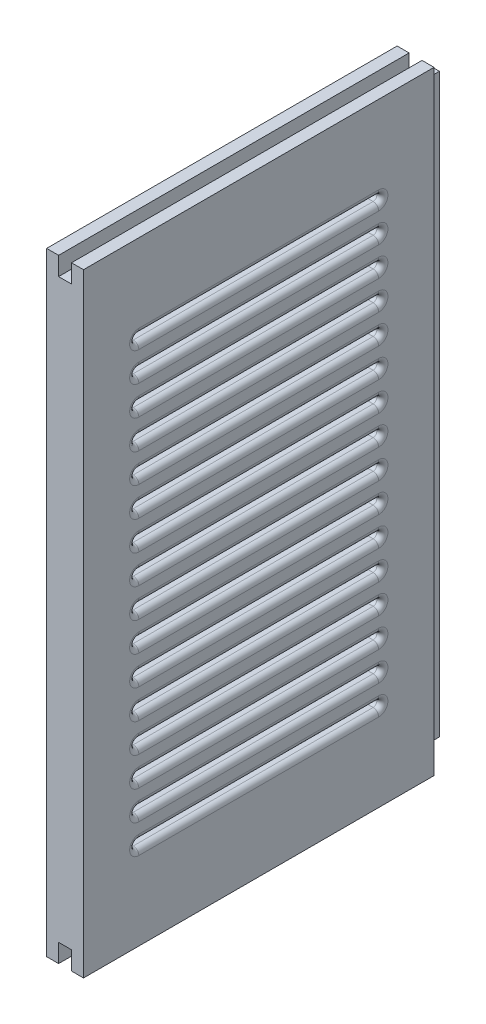
SolidWorks part; units mm, degrees
ref_plane "Front Plane" through (0, 0, 0) normal (1, 0, 0) x (0, 1, 0)
ref_plane "Top Plane" through (0, 0, 0) normal (0, 0, 1) x (0, 1, 0)
ref_plane "Right Plane" through (0, 0, 0) normal (0, 1, 0) x (-1, 0, 0)
sketch "Sketch1" plane through (0, 0, 0) normal (1, 0, 0) x (0, 1, 0)
  line L1 (0, 0) -> (166.25, 0)
  line L2 (0, 0) -> (0, 95)
  line L3 (0, 95) -> (166.25, 95)
  line L4 (166.25, 0) -> (166.25, 95)
  dimension "D1" = 166.25
  dimension "D2" = 95
extrude "Boss-Extrude1" add sketch "Sketch1" against normal blind 10
sketch "Sketch2" plane through (0, 166.25, 0) normal (0, 1, 0) x (-1, 0, 0)
  line L0 (0, 0) -> (3.35, 0) construction
  line L1 (0, 0) -> (0, -4.8) construction
  line L2 (0, -4.8) -> (3.35, -4.8) construction
  line L3 (3.35, 0) -> (3.35, -4.8) construction
  line L4 (10, 0) -> (6.65, 0) construction
  line L5 (10, 0) -> (10, -4.8) construction
  line L6 (10, -4.8) -> (6.65, -4.8) construction
  line L7 (6.65, 0) -> (6.65, -4.8) construction
  line L8 (6.65, -4.8) -> (3.35, -4.8)
  line L9 (6.65, -4.8) -> (6.65, 0)
  line L10 (6.65, 0) -> (3.35, 0)
  line L11 (3.35, -4.8) -> (3.35, 0)
  line L14 (10, 0) -> (0, 0) construction
  dimension "D1" = 3.35
  dimension "D2" = 3.35
  dimension "D3" = 4.8
extrude "Boss-Extrude2" add sketch "Sketch2" against normal up to surface (166.25 mm away) up to face at (-5, 0, 47.5)
ref_plane "Plane1" through (0, 83.125, 0) normal (0, 1, 0) x (1, 0, 0)
sketch "Sketch3" plane through (0, 166.25, 0) normal (0, 1, 0) x (-1, 0, 0)
  line L0 (0, 95) -> (3.25, 95) construction
  line L1 (0, 95) -> (0, -4.8) construction
  line L2 (0, -4.8) -> (3.25, -4.8) construction
  line L3 (3.25, 95) -> (3.25, -4.8) construction
  line L4 (6.75, -4.8) -> (10, -4.8) construction
  line L5 (6.75, -4.8) -> (6.75, 95) construction
  line L6 (6.75, 95) -> (10, 95) construction
  line L7 (10, -4.8) -> (10, 95) construction
  line L8 (3.25, 95) -> (6.75, 95)
  line L9 (3.25, 95) -> (3.25, -4.8)
  line L10 (3.25, -4.8) -> (6.75, -4.8)
  line L11 (6.75, 95) -> (6.75, -4.8)
  line L14 (10, 95) -> (0, 95) construction
  line L16 (3.35, -4.8) -> (6.65, -4.8) construction
  dimension "D1" = 3.25
  dimension "D2" = 3.25
extrude "Cut-Extrude1" cut sketch "Sketch3" against normal blind 5
mirror "Mirror1" about plane through (0, 83.125, 0) normal (0, 1, 0) of "Cut-Extrude1"
sketch "Sketch4" plane through (-10, 0, 0) normal (-1, 0, 0) x (0, -1, 0)
  line L0 (-166.25, 95) -> (0, 95) construction
  line L1 (-161.25, 0) -> (-5, 0)
  line L2 (-161.25, 0) -> (-161.25, 95)
  line L3 (-161.25, 95) -> (-5, 95)
  line L4 (-5, 0) -> (-5, 95)
  line L5 (-156.25, 5) -> (-156.25, 90)
  line L6 (-156.25, 90) -> (-10, 90)
  line L7 (-10, 5) -> (-10, 90)
  line L8 (-156.25, 5) -> (-10, 5)
  dimension "D1" = 5
extrude "Cut-Extrude2" cut sketch "Sketch4" against normal blind 5 contours L5 L8 L7 L6 region at (-10, 83.125, 47.5)
chamfer "Chamfer1" distance 5 distance2 2.5 4 edges at (-10, 10, 47.5) (-10, 83.125, 5) (-10, 156.25, 47.5) (-10, 83.125, 90) first distance on face at (-7.5, 10, 47.5) first distance on face at (-7.5, 83.125, 5) first distance on face at (-7.5, 156.25, 47.5) first distance on face at (-7.5, 83.125, 90)
sketch "Sketch5" plane through (-5, 0, 0) normal (-1, 0, 0) x (0, -1, 0)
  line L0 (-10, 5) -> (-10, 90) construction
  line L1 (-156.25, 90) -> (-10, 90) construction
  line L2 (-156.25, 90) -> (-156.25, 80) construction
  line L3 (-156.25, 80) -> (-10, 80) construction
  line L4 (-10, 90) -> (-10, 80) construction
  line L5 (-156.25, 5) -> (-156.25, 90) construction
  line L6 (-10, 80) -> (-156.25, 80) construction
  line L7 (-10, 80) -> (-10, 15) construction
  line L8 (-10, 15) -> (-156.25, 15) construction
  line L9 (-156.25, 80) -> (-156.25, 15) construction
  line L10 (-142.5, 80) -> (-142.5, 15) construction
  line L11 (-156.25, 15) -> (-10, 15) construction
  line L12 (-156.25, 15) -> (-156.25, 5) construction
  line L13 (-156.25, 5) -> (-10, 5) construction
  line L14 (-10, 15) -> (-10, 5) construction
  line L15 (-141.5, 80) -> (-141.5, 15)
  line L16 (-143.5, 80) -> (-143.5, 15)
  line L18 (-166.25, 95) -> (-142.5, 95) construction
  line L19 (-166.25, 95) -> (-166.25, 80) construction
  line L20 (-166.25, 80) -> (-142.5, 80) construction
  line L21 (-142.5, 95) -> (-142.5, 80) construction
  arc A0 (-141.5, 80) -> (-143.5, 80) centre (-142.5, 80) ccw
  arc A1 (-143.5, 15) -> (-141.5, 15) centre (-142.5, 15) ccw
  point P16 (-142.5, 47.5)
  dimension "D1" = 10
  dimension "D3" = 146.25
  dimension "D4" = 23.75
extrude "Cut-Extrude3" cut sketch "Sketch5" against normal up to next
fillet "Fillet1" radius 1.5 8 edges at (0, 142.5, 81) (0, 143.5, 47.5) (0, 142.5, 14) (-5, 142.5, 81) (-5, 141.5, 47.5) (-5, 142.5, 14) (0, 141.5, 47.5) (-5, 143.5, 47.5)
pattern_linear "LPattern1" count 16 spacing 7.9167 along (0, -1, 0) of "Cut-Extrude3", "Fillet1"
equation "\"whitekey_cutout_length\"= 101.5"
equation "\"whitekey_spacing\"=1.25"
equation "\"key_mount_recess_length\"=50"
equation "\"key_mount_recess_height\"=12.5"
equation "\"key_mount_recess_depth\"=1.5"
equation "\"wall_thickness\"=10"
equation "\"guide_brace_height\"=20"
equation "\"guide_brace_thickness\"=2"
equation "\"dowel_recess_depth\"=10"
equation "\"dowel_recess_offset\"=3.25"
equation "\"dowel_insert_tolerance\"=0.1"
equation "\"base_mount_height\"=40"
equation "\"base_rear_length\"=80"
equation "\"base_front_length\"=111.5"
equation "\"screw_hole_wall_offset\"=7.25"
equation "\"screw_hole_edge_inset\"=\"dowel_recess_depth\"/2"
equation "\"screw_hole_diameter\"=3.8"
equation "\"screw_head_hole_diameter\"=6.7"
equation "\"screw_nut_hole_side_len\"=3.5"
equation "\"screw_nut_recess_offset\"=0.35"
equation "\"screw_head_and_nut_recess_depth\"=2.5"
equation "\"screw_shaft_diameter\"=3.5"
equation "\"switch_board_width\"=30"
equation "\"switch_board_thickness\"=1.6"
equation "\"switch_board_wall_offset\"=11.5"
equation "\"heatset_insert_hole_diameter\"=4.8"
equation "\"heatset_insert_hole_depth\"=3.8"
equation "\"front_rear_panel_width\"=23.75"
equation "\"front_panel_height\"=24"
equation "\"front_rear_panel_recess_depth\"=5"
equation "\"rod_diameter\"=5"
equation "\"rod_head_diameter\"=8"
equation "\"rod_length_adj\"=0.5"
equation "\"rod_insert_length\"=2.8"
equation "\"switch_black_key_mount_height\"=8"
equation "\"switch_white_key_mount_height\"=3"
equation "\"side_panel_depth\"=35"
equation "\"interface_panel_height\"=135"
equation "\"interface_panel_roof_length\"=50"
equation "\"rear_center_panel_height_adjust\"=50"
equation "\"D1@Sketch1\"=\"front_rear_panel_width\"*7"
equation "\"D2@Sketch1\"=\"interface_panel_height\"+\"wall_thickness\"-\"rear_center_panel_height_adjust\""
equation "\"D1@Boss-Extrude1\"=\"wall_thickness\""
equation "\"D2@Sketch2\"=\"dowel_recess_offset\"+\"dowel_insert_tolerance\""
equation "\"D1@Sketch2\"=\"dowel_recess_offset\"+\"dowel_insert_tolerance\""
equation "\"D3@Sketch2\"=\"front_rear_panel_recess_depth\"-\"dowel_insert_tolerance\"*2"
equation "\"D2@Sketch3\"=\"dowel_recess_offset\""
equation "\"D1@Sketch3\"=\"dowel_recess_offset\""
equation "\"D1@Cut-Extrude1\"=\"front_rear_panel_recess_depth\""
equation "\"D1@Cut-Extrude2\"=\"wall_thickness\"/2"
equation "\"D4@Sketch5\"=\"front_rear_panel_width\""
equation "\"D3@LPattern1\"=\"front_rear_panel_width\"/3"
